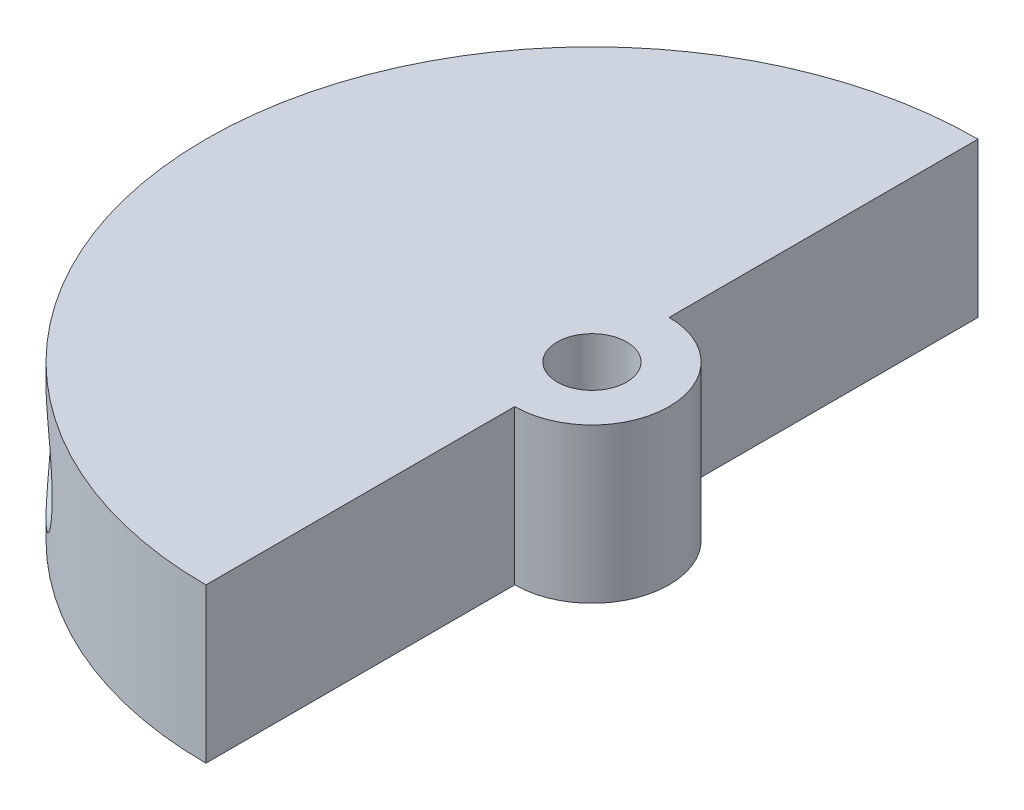
SolidWorks part; units mm, degrees
ref_plane "Alzado" through (0, 0, 0) normal (0, 0, 1) x (1, 0, 0)
ref_plane "Planta" through (0, 0, 0) normal (0, 1, 0) x (1, 0, 0)
ref_plane "Vista lateral" through (0, 0, 0) normal (1, 0, 0) x (0, 0, -1)
sketch "Croquis1" plane through (0, 0, 0) normal (0, 1, 0) x (1, 0, 0)
  line L0 (0, 2) -> (0, 10)
  line L1 (0, -2) -> (0, -10)
  arc A0 (0, 10) -> (0, -10) centre (0, 0) ccw
  arc A1 (0, -2) -> (0, 2) centre (0, 0) ccw
  circle A2 centre (0, 0) radius 0.9
  dimension "D1" = 2
  dimension "D2" = 10
  dimension "D3" = 1.8
extrude "Saliente-Extruir1" add sketch "Croquis1" along normal blind 4
ref_plane "Plano1" through (-10, 0, 0) normal (-1, 0, 0) x (0, 0, 1)
ref_plane "Plano2" through (-7.0711, 0, -7.0711) normal (-0.7071, 0, -0.7071) x (0, -1, 0)
ref_plane "Plano3" through (-7.0711, 0, 7.0711) normal (-0.7071, 0, 0.7071) x (0, -1, 0)
ref_axis "Eje1" through (2.4375, 4, 16.5797) along (-0.7071, 0, -0.7071)
ref_axis "Eje2" through (0, 4, 0) along (0, -1, 0)
ref_plane "Plano4" through (0, 0, 0) normal (-0.7071, 0, -0.7071) x (0, -1, 0)
ref_plane "Plano5" through (0, 0, 0) normal (0, 0, -1) x (0, -1, 0)
ref_plane "Plano6" through (0, 0, 0) normal (0.7071, 0, -0.7071) x (0, -1, 0)
ref_axis "Eje3" through (-7.0711, 9.1722, 7.0711) along (0, -1, 0)
ref_axis "Eje4" through (-10, 4.2, 0) along (0, -1, 0)
ref_axis "Eje5" through (-7.0711, 5.968, -7.0711) along (0, -1, 0)
ref_plane "Plano7" through (0, 2, 0) normal (0, 1, 0) x (1, 0, 0)
ref_point "Punto1"
ref_point "Punto2"
ref_point "Punto3"
sketch "Croquis5" plane through (-7.0711, 0, -7.0711) normal (-0.7071, 0, -0.7071) x (0, -1, 0)
  circle A0 centre (-2, 0) radius 1.5
  dimension "D1" = 3
extrude "Cortar-Extruir1" cut sketch "Croquis5" against normal blind 6
sketch "Croquis6" plane through (-10, 0, 0) normal (-1, 0, 0) x (0, 0, 1)
  circle A0 centre (0, 2) radius 1.5
  dimension "D1" = 3
extrude "Cortar-Extruir2" cut sketch "Croquis6" against normal blind 6
sketch "Croquis7" plane through (-7.0711, 0, 7.0711) normal (-0.7071, 0, 0.7071) x (0, -1, 0)
  circle A0 centre (-2, 0) radius 1.5
  dimension "D1" = 3
extrude "Cortar-Extruir3" cut sketch "Croquis7" against normal blind 6
